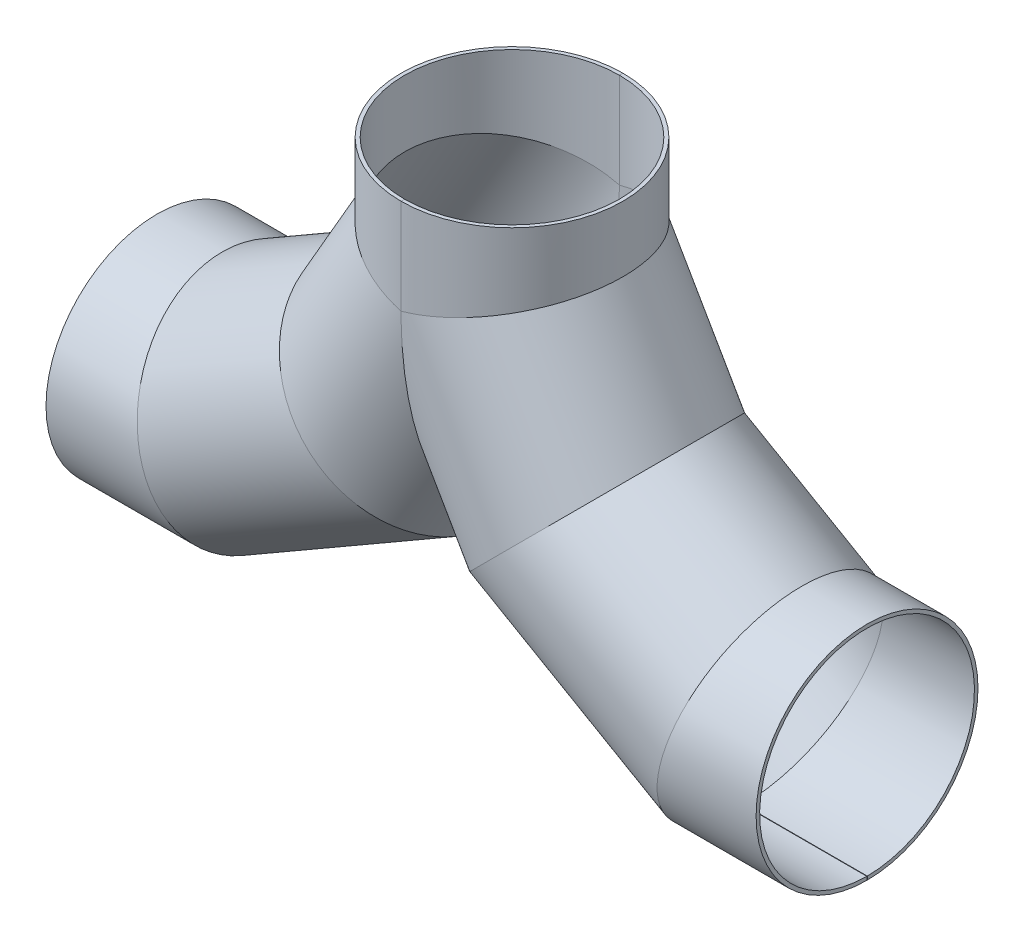
SolidWorks part; units mm, degrees
ref_plane "前视基准面" through (0, 0, 0) normal (0, 0, 1) x (1, 0, 0)
ref_plane "上视基准面" through (0, 0, 0) normal (0, 1, 0) x (1, 0, 0)
ref_plane "右视基准面" through (0, 0, 0) normal (1, 0, 0) x (0, 0, -1)
sketch "草图1" plane through (0, 0, 0) normal (0, 0, 1) x (1, 0, 0)
  line L0 (0, -1050) -> (0, 0) construction
  line L1 (0, -214.3594) -> (214.3594, -585.6406) construction
  line L2 (214.3594, -585.6406) -> (585.6406, -800) construction
  line L3 (585.6406, -800) -> (800, -800) construction
  line L4 (-250, 0) -> (250, 0) construction
  line L5 (0, -1050) -> (0, -1058) construction
  line L6 (0, 0) -> (0, 4) construction
  line L7 (0, 0) -> (800, 0) construction
  line L8 (800, 0) -> (800, -800) construction
  line L9 (214.3594, -585.6406) -> (800, 0) construction
  line L10 (800, 0) -> (585.6406, -800) construction
  line L11 (0, -214.3594) -> (800, 0) construction
  line L12 (800, 0) -> (400, -692.8203) construction
  line L13 (800, 0) -> (107.1797, -400) construction
  line L14 (800, -1050) -> (800, -550) construction
  line L15 (800, -1050) -> (518.6533, -1050) construction
  line L16 (518.6533, -1050) -> (31.3467, -768.6533) construction
  line L17 (31.3467, -768.6533) -> (-250, -281.3467) construction
  line L18 (-250, -281.3467) -> (-250, 0) construction
  line L19 (214.3594, -585.6406) -> (31.3467, -768.6533) construction
  line L20 (0, -214.3594) -> (-250, -281.3467) construction
  line L21 (518.6533, -1050) -> (585.6406, -800) construction
  line L22 (250, 0) -> (250, -147.3721) construction
  line L23 (250, -147.3721) -> (397.3721, -402.6279) construction
  line L24 (397.3721, -402.6279) -> (652.6279, -550) construction
  line L25 (652.6279, -550) -> (800, -550) construction
  line L26 (0, -1050) -> (0, 0)
  dimension "d" = 500
  dimension "t" = 8
  dimension "nm" = 4
  dimension "R" = 800
  dimension "D3" = 30
sketch "草图2" plane through (0, 0, 0) normal (0, 1, 0) x (1, 0, 0)
  line L0 (800, 250) -> (800, -250) construction
  line L1 (0, 250) -> (0, -250) construction
  circle A0 centre (0, 0) radius 250
extrude "拉伸-薄壁1" add sketch "草图2" against normal up to vertex (281.3467 mm away) thin up to point (-250, -281.3467, 0) thin type one direction reverse wall 8
ref_plane "基准面1" through (200, -346.4102, 0) normal (0.5, -0.866, 0) x (0.866, 0.5, 0)
sketch "草图3" plane through (200, -346.4102, 0) normal (0.5, -0.866, 0) x (0.866, 0.5, 0)
  circle A0 centre (-107.1797, 0) radius 250
extrude "拉伸-薄壁2" add sketch "草图3" against normal up to vertex (281.3467 mm away) and the other way up to vertex (281.3467 mm away) separate body thin up to point (-250, -281.3467, 0) other way up to point (31.3467, -768.6533, 0) thin type one direction reverse wall 8
ref_plane "基准面2" through (600, -346.4102, 0) normal (0.866, -0.5, 0) x (0, 0, -1)
sketch "草图4" plane through (600, -346.4102, 0) normal (0.866, -0.5, 0) x (0, 0, -1)
  circle A0 centre (0, -400) radius 250
extrude "拉伸-薄壁3" add sketch "草图4" against normal up to vertex (281.3467 mm away) and the other way up to vertex (281.3467 mm away) separate body thin up to point (31.3467, -768.6533, 0) other way up to point (518.6533, -1050, 0) thin type one direction reverse wall 8
ref_plane "基准面3" through (800, 0, 0) normal (1, 0, 0) x (0, 0, -1)
sketch "草图5" plane through (800, 0, 0) normal (1, 0, 0) x (0, 0, -1)
  circle A0 centre (0, -800) radius 250
extrude "拉伸-薄壁4" add sketch "草图5" against normal up to vertex (281.3467 mm away) separate body thin up to point (518.6533, -1050, 0) thin type one direction reverse wall 8
sketch "草图6" plane through (0, 0, 0) normal (0, 0, 1) x (1, 0, 0)
  line L0 (800, 0) -> (-250, -281.3467)
extrude "切除-拉伸1" cut sketch "草图6" against normal through all and the other way through all
extrude "切除-拉伸2" cut sketch "草图6<2>" against normal through all and the other way through all flip side to cut
sketch "草图6<2>" plane through (0, 0, 0) normal (0, 0, 1) x (1, 0, 0) same geometry as "草图6"
sketch "草图7" plane through (0, 0, 0) normal (0, 0, 1) x (1, 0, 0)
  line L0 (800, 0) -> (31.3467, -768.6533)
extrude "切除-拉伸3" cut sketch "草图7" against normal through all and the other way through all
extrude "切除-拉伸4" cut sketch "草图7<2>" against normal through all and the other way through all flip side to cut
sketch "草图7<2>" plane through (0, 0, 0) normal (0, 0, 1) x (1, 0, 0) same geometry as "草图7"
sketch "草图8" plane through (0, 0, 0) normal (0, 0, 1) x (1, 0, 0)
  line L0 (800, 0) -> (518.6533, -1050)
extrude "切除-拉伸5" cut sketch "草图8" against normal through all and the other way through all
extrude "切除-拉伸6" cut sketch "草图8<2>" against normal through all and the other way through all flip side to cut
sketch "草图8<2>" plane through (0, 0, 0) normal (0, 0, 1) x (1, 0, 0) same geometry as "草图8"
sketch "草图9" plane through (200, -346.4102, 0) normal (0.5, -0.866, 0) x (0.866, 0.5, 0)
  line L0 (-107.1797, 0) -> (-357.1797, 0)
  circle A0 centre (-107.1797, 0) radius 250 construction
extrude "切除-拉伸-薄壁1" cut sketch "草图9" against normal through all and the other way through all thin thin type mid plane wall 1
sketch "草图10" plane through (600, -346.4102, 0) normal (0.866, -0.5, 0) x (0, 0, -1)
  line L0 (0, -400) -> (0, -650)
  circle A0 centre (0, -400) radius 250 construction
extrude "切除-拉伸-薄壁2" cut sketch "草图10" against normal through all and the other way through all thin thin type mid plane wall 1
sketch "草图11" plane through (800, 0, 0) normal (1, 0, 0) x (0, 0, -1)
  line L0 (0, -800) -> (0, -1050)
  circle A0 centre (0, -800) radius 250 construction
extrude "切除-拉伸-薄壁4" cut sketch "草图11" against normal through all thin thin type mid plane wall 1
extrude "切除-拉伸8" cut sketch "草图1" against normal through all and the other way through all
mirror "镜向1" about plane through (0, 0, 0) normal (1, 0, 0) of bodies 115 114 117 116
equation "\"D5@拉伸-薄壁1\" = \"t@草图1\""
equation "\"D5@拉伸-薄壁2\" = \"t@草图1\""
equation "\"D5@拉伸-薄壁3\" = \"t@草图1\""
equation "\"D5@拉伸-薄壁4\" = \"t@草图1\""
